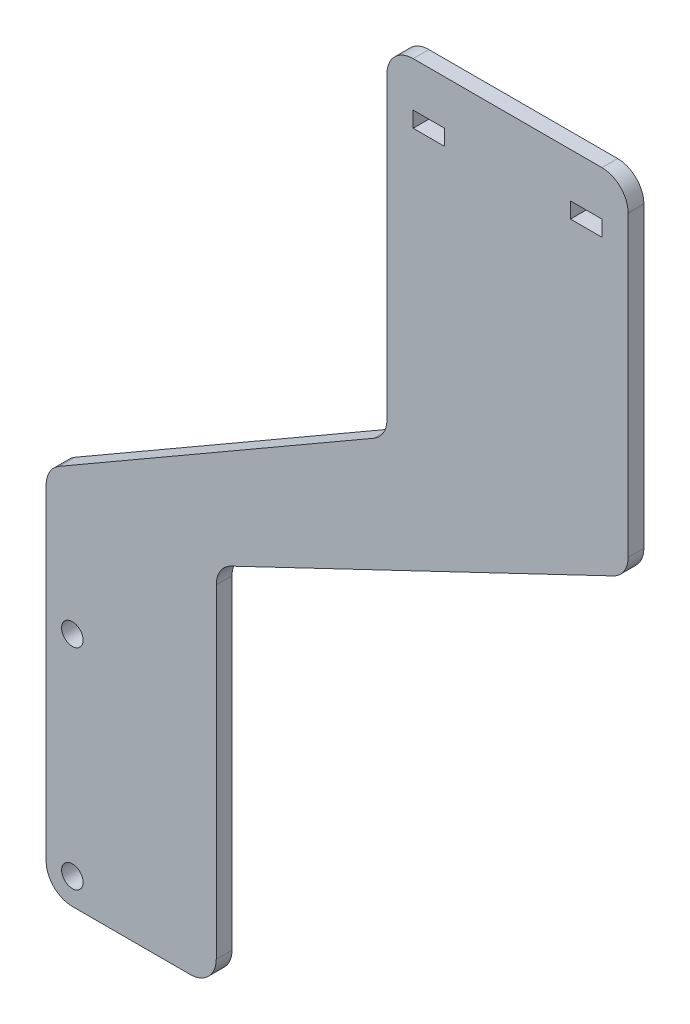
SolidWorks part; units mm, degrees
ref_plane "Front Plane" through (0, 0, 0) normal (0, 0, 1) x (1, 0, 0)
ref_plane "Top Plane" through (0, 0, 0) normal (0, 1, 0) x (1, 0, 0)
ref_plane "Right Plane" through (0, 0, 0) normal (1, 0, 0) x (0, 0, -1)
sketch "Sketch1" plane through (0, 0, 0) normal (0, 0, 1) x (1, 0, 0)
  line L0 (-78.6038, -5.5278) -> (-111.0529, -5.5278)
  line L1 (-111.0529, -5.5278) -> (-111.0529, 64.4722)
  line L3 (-46.0529, 102) -> (-46.0529, 167)
  line L4 (-46.0529, 167) -> (-0.0529, 167)
  line L5 (-0.0529, 167) -> (-0.0529, 102)
  line L6 (-106.0529, 39.4722) -> (-106.0529, -18.7631) construction
  line L7 (-23.0529, 167) -> (-23.0529, 157) construction
  line L8 (-23.0529, 157) -> (-1.1451, 157) construction
  line L9 (-35.0529, 158.5) -> (-35.0529, 155.5)
  line L10 (-11.0529, 158.5) -> (-5.0529, 158.5)
  line L11 (-11.0529, 158.5) -> (-11.0529, 155.5)
  line L12 (-11.0529, 155.5) -> (-5.0529, 155.5)
  line L13 (-5.0529, 158.5) -> (-5.0529, 155.5)
  line L14 (-11.0529, 158.5) -> (-5.0529, 155.5) construction
  line L15 (-11.0529, 155.5) -> (-5.0529, 158.5) construction
  line L16 (-35.0529, 155.5) -> (-41.0529, 155.5)
  line L17 (-41.0529, 158.5) -> (-41.0529, 155.5)
  line L18 (-35.0529, 158.5) -> (-41.0529, 158.5)
  line L19 (-46.0529, 102) -> (-111.0529, 64.4722)
  line L21 (-0.0529, 102) -> (-46.0529, 102) construction
  line L22 (-78.6038, 45.0439) -> (-78.6038, -5.5278)
  line L23 (-111.0529, 64.4722) -> (-78.6038, 64.4722) construction
  line L24 (-78.6038, 45.0439) -> (-78.6038, 64.4722)
  line L25 (-78.6038, 64.4722) -> (-0.0529, 102)
  circle A0 centre (-106.0529, 39.4722) radius 2.05
  circle A1 centre (-106.0529, -0.5278) radius 2.05
  point P15 (-8.0529, 157)
  dimension "D1" = 4.1
  dimension "D3" = 5
  dimension "D7" = 40
  dimension "D2" = 5
  dimension "D4" = 60
  dimension "D5" = 46
  dimension "D6" = 120
  dimension "D8" = 70
  dimension "D9" = 6
  dimension "D10" = 3
  dimension "D11" = 15
  dimension "D12" = 10
  dimension "D13" = 65
extrude "Boss-Extrude1" add sketch "Sketch1" along normal blind 3
fillet "Fillet1" radius 5 8 edges at (-46.0529, 167, 1.5) (-0.0529, 167, 1.5) (-111.0529, -5.5278, 1.5) (-46.0529, 102, 1.5) (-111.0529, 64.4722, 1.5) (-78.6038, -5.5278, 1.5) (-78.6038, 64.4722, 1.5) (-0.0529, 102, 1.5)
